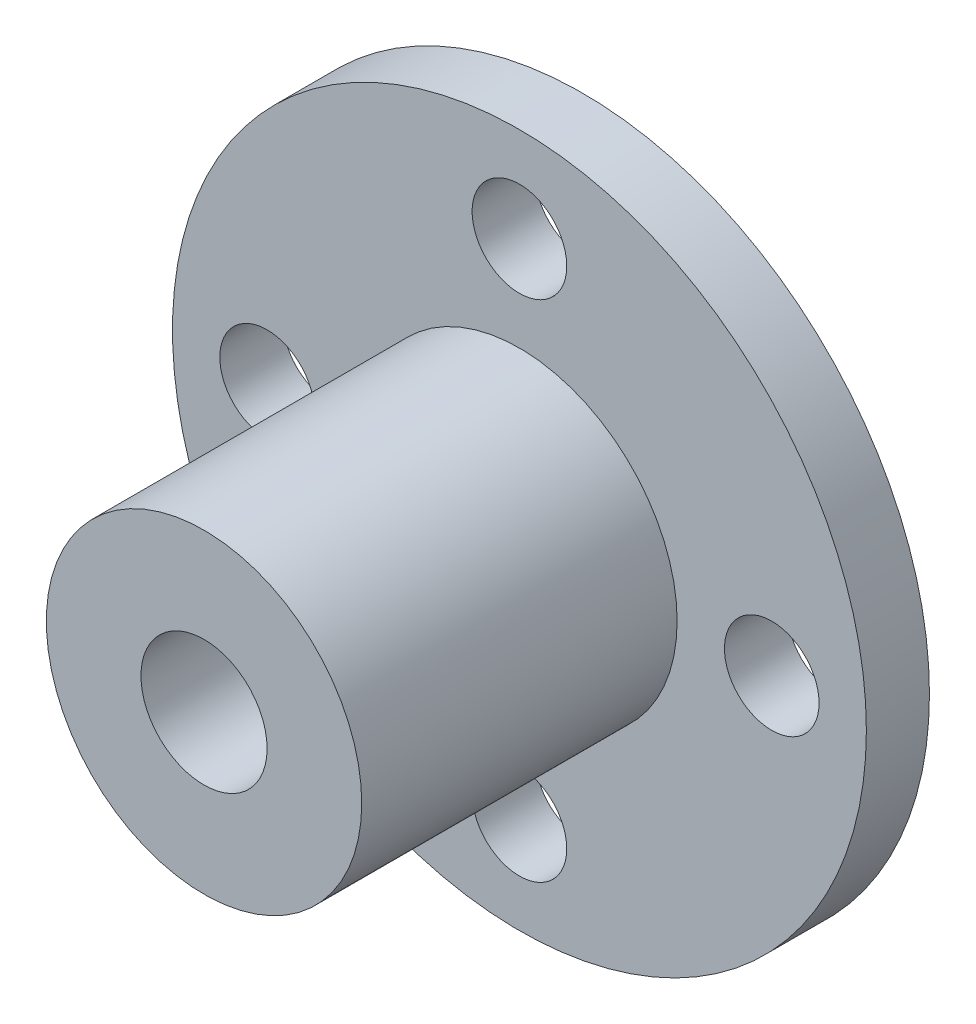
SolidWorks part; units mm, degrees
material "1060 Alloy"
ref_plane "Front Plane" through (0, 0, 0) normal (0, 0, 1) x (1, 0, 0)
ref_plane "Top Plane" through (0, 0, 0) normal (0, 1, 0) x (1, 0, 0)
ref_plane "Right Plane" through (0, 0, 0) normal (1, 0, 0) x (0, 0, -1)
sketch "Sketch1" plane through (0, 0, 0) normal (0, 0, 1) x (1, 0, 0)
  line L0 (-8, 0) -> (0, 0) construction
  line L1 (0, 0) -> (0, -8) construction
  line L2 (0, 8) -> (0, 0) construction
  line L3 (8, 0) -> (0, 0) construction
  circle A0 centre (0, 0) radius 2
  circle A1 centre (0, 0) radius 5
  circle A2 centre (0, 0) radius 11
  circle A3 centre (0, 8) radius 1.5
  circle A4 centre (8, 0) radius 1.5
  circle A5 centre (0, -8) radius 1.5
  circle A6 centre (-8, 0) radius 1.5
  point P13 (0, 6.5)
  point P14 (0, 2)
  point P15 (0, -6.5)
  dimension "D1" = 3
  dimension "D2" = 10
  dimension "D3" = 4
  dimension "D4" = 22
  dimension "D5" = 4.5
extrude "Boss-Extrude1" add sketch "Sketch1" along normal blind 2 contours A2 A6 A5 A4 A3 A1 region at (-10.6889, 0, 0)
extrude "Boss-Extrude2" add sketch "Sketch1<3>" along normal blind 12 contours A1 A0 region at (-4.8586, 0, 0)
sketch "Sketch1<3>" plane through (0, 0, 0) normal (0, 0, 1) x (1, 0, 0) same geometry as "Sketch1"
